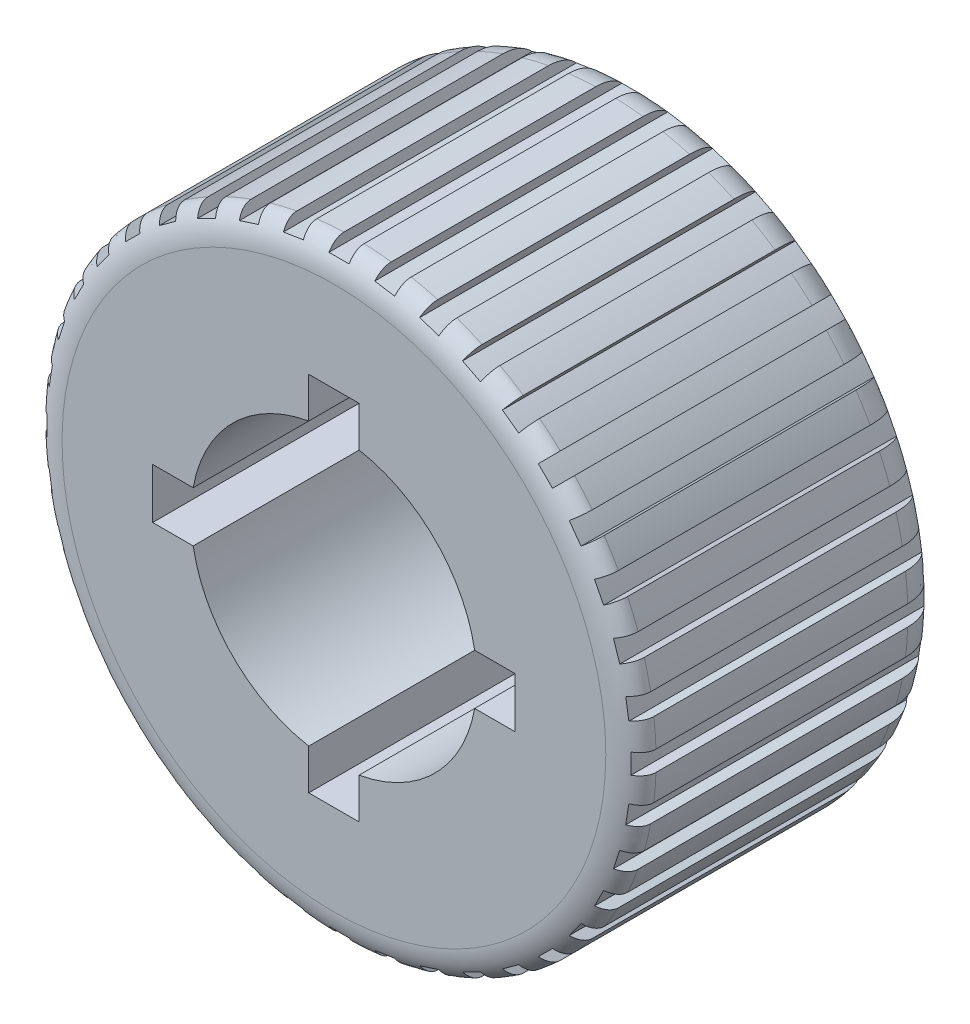
SolidWorks part; units mm, degrees
ref_plane "Plano frontal" through (0, 0, 0) normal (0, 0, 1) x (1, 0, 0)
ref_plane "Plano superior" through (0, 0, 0) normal (0, 1, 0) x (1, 0, 0)
ref_plane "Plano direito" through (0, 0, 0) normal (1, 0, 0) x (0, 0, -1)
sketch "Esboço1" plane through (0, 0, 0) normal (0, 0, 1) x (1, 0, 0)
  circle A0 centre (0, 0) radius 30
  circle A1 centre (0, 0) radius 10.7
  circle A2 centre (0, 0) radius 6.1
  circle A3 centre (0, 0) radius 8.9
  circle A4 centre (0, 0) radius 4.3
  dimension "D1" = 60
extrude "Ressalto-extrusão1" add sketch "Esboço1" along normal blind 30 contours A0 A1 region at (-29.1515, 0, 0)
sketch "Esboço2" plane through (0, 0, 0) normal (0, 0, -1) x (-1, 0, 0)
  circle A1 centre (0, 0) radius 10.7 construction
  circle A3 centre (0, 0) radius 10.7
  circle A4 centre (0, 0) radius 14.2
  dimension "D1" = 28.4
extrude "Corte-extrusão1" cut sketch "Esboço2" against normal through all
sketch "Esboço4" plane through (0, 0, 0) normal (0, 1, 0) x (1, 0, 0)
  line L0 (-29, -8.5) -> (-29, -9.5)
  line L2 (-30, -2) -> (-30, -3)
  line L4 (0, 0) -> (0, 11.1523) construction
  line L6 (-29, -29) -> (-30, -29)
  line L7 (-30, -8.5) -> (-30, -9.5)
  line L8 (-29, -35.5) -> (-30, -35.5)
  line L9 (-30, -35.5) -> (-30, -34.5)
  line L10 (-30, -34.5) -> (-29, -34.5)
  line L11 (-30, -29) -> (-30, -28)
  line L12 (-30, -28) -> (-29, -28)
  line L14 (-29, -22.5) -> (-30, -22.5)
  line L15 (-30, -22.5) -> (-30, -21.5)
  line L16 (-30, -21.5) -> (-29, -21.5)
  line L17 (-29, -28) -> (-29, -29)
  line L18 (-29, -16) -> (-30, -16)
  line L19 (-30, -16) -> (-30, -15)
  line L20 (-30, -15) -> (-29, -15)
  line L21 (-29, -21.5) -> (-29, -22.5)
  line L22 (-29, -9.5) -> (-30, -9.5)
  line L23 (-30, -9.5) -> (-30, -8.5)
  line L24 (-30, -8.5) -> (-29, -8.5)
  line L25 (-29, -15) -> (-29, -16)
  line L26 (-29, -3) -> (-30, -3)
  line L27 (-30, -3) -> (-30, -2)
  line L28 (-30, -2) -> (-29, -2)
  line L30 (-29, -2) -> (-29, -3)
  line L31 (-30, -15) -> (-30, -16)
  line L32 (-29, -34.5) -> (-29, -35.5)
  line L33 (-30, 4.5) -> (-29, 4.5)
  line L34 (-30, 3.5) -> (-30, 4.5)
  line L35 (-29, 3.5) -> (-30, 3.5)
  line L37 (-30, -21.5) -> (-30, -22.5)
  line L38 (-30, -28) -> (-30, -29)
  line L39 (-30, -34.5) -> (-30, -35.5)
  point P0 (0, 0)
  dimension "D1" = 7
  dimension "D2" = 29
  dimension "D3" = 30
  dimension "D4" = 2
  dimension "D5" = 3
  dimension "D6" = 8.5
sketch "Esboço5" plane through (0, 0, 30) normal (0, 0, 1) x (1, 0, 0)
  line L0 (0, 0) -> (-39.2966, 0) construction
  line L5 (-1, 29.9833) -> (-1, 28.9828)
  line L6 (1, 29.9833) -> (1, 28.9828)
  arc A3 (1, 29.9833) -> (-1, 29.9833) centre (0, 0) ccw
  arc A4 (1, 28.9828) -> (-1, 28.9828) centre (0, 0) ccw
fillet "Filete2" radius 2 2 edges at (30, 0, 0) (30, 0, 30) second distance 3 first distance on face at (-14.2, 0, 0) first distance on face at (30, 0, 30)
sketch "Esboço6" plane through (0, 0, 30) normal (0, 0, 1) x (1, 0, 0)
  line L0 (5.5216, 28.4695) -> (5.6781, 29.4577)
  line L1 (3.7027, 29.7706) -> (3.5462, 28.7824)
  line L2 (-1, 29.9833) -> (-1, 28.9828)
  line L3 (1, 28.9828) -> (1, 29.9833)
  line L4 (-1, 29.9833) -> (-1, 28.9828)
  line L5 (1, 28.9828) -> (1, 29.9833)
  line L6 (9.9072, 27.2552) -> (10.2164, 28.2068)
  line L7 (8.3143, 28.8249) -> (8.0051, 27.8733)
  line L8 (14.0489, 25.3698) -> (14.5032, 26.2614)
  line L9 (12.7211, 27.1693) -> (12.2669, 26.2778)
  line L10 (17.8447, 22.8598) -> (18.4328, 23.6692)
  line L11 (16.8147, 24.8448) -> (16.2266, 24.0353)
  line L12 (21.201, 19.7868) -> (21.9085, 20.4943)
  line L13 (20.4943, 21.9085) -> (19.7868, 21.201)
  line L14 (24.0353, 16.2266) -> (24.8448, 16.8147)
  line L15 (23.6692, 18.4328) -> (22.8598, 17.8447)
  line L16 (26.2778, 12.2669) -> (27.1693, 12.7211)
  line L17 (26.2614, 14.5032) -> (25.3698, 14.0489)
  line L18 (27.8733, 8.0051) -> (28.8249, 8.3143)
  line L19 (28.2068, 10.2164) -> (27.2552, 9.9072)
  line L20 (28.7824, 3.5462) -> (29.7706, 3.7027)
  line L21 (29.4577, 5.6781) -> (28.4695, 5.5216)
  line L22 (28.9828, -1) -> (29.9833, -1)
  line L23 (29.9833, 1) -> (28.9828, 1)
  line L24 (28.4695, -5.5216) -> (29.4577, -5.6781)
  line L25 (29.7706, -3.7027) -> (28.7824, -3.5462)
  line L26 (27.2552, -9.9072) -> (28.2068, -10.2164)
  line L27 (28.8249, -8.3143) -> (27.8733, -8.0051)
  line L28 (25.3698, -14.0489) -> (26.2614, -14.5032)
  line L29 (27.1693, -12.7211) -> (26.2778, -12.2669)
  line L30 (22.8598, -17.8447) -> (23.6692, -18.4328)
  line L31 (24.8448, -16.8147) -> (24.0353, -16.2266)
  line L32 (19.7868, -21.201) -> (20.4943, -21.9085)
  line L33 (21.9085, -20.4943) -> (21.201, -19.7868)
  line L34 (16.2266, -24.0353) -> (16.8147, -24.8448)
  line L35 (18.4328, -23.6692) -> (17.8447, -22.8598)
  line L36 (12.2669, -26.2778) -> (12.7211, -27.1693)
  line L37 (14.5032, -26.2614) -> (14.0489, -25.3698)
  line L38 (8.0051, -27.8733) -> (8.3143, -28.8249)
  line L39 (10.2164, -28.2068) -> (9.9072, -27.2552)
  line L40 (3.5462, -28.7824) -> (3.7027, -29.7706)
  line L41 (5.6781, -29.4577) -> (5.5216, -28.4695)
  line L42 (-1, -28.9828) -> (-1, -29.9833)
  line L43 (1, -29.9833) -> (1, -28.9828)
  line L44 (-5.5216, -28.4695) -> (-5.6781, -29.4577)
  line L45 (-3.7027, -29.7706) -> (-3.5462, -28.7824)
  line L46 (-9.9072, -27.2552) -> (-10.2164, -28.2068)
  line L47 (-8.3143, -28.8249) -> (-8.0051, -27.8733)
  line L48 (-14.0489, -25.3698) -> (-14.5032, -26.2614)
  line L49 (-12.7211, -27.1693) -> (-12.2669, -26.2778)
  line L50 (-17.8447, -22.8598) -> (-18.4328, -23.6692)
  line L51 (-16.8147, -24.8448) -> (-16.2266, -24.0353)
  line L52 (-21.201, -19.7868) -> (-21.9085, -20.4943)
  line L53 (-20.4943, -21.9085) -> (-19.7868, -21.201)
  line L54 (-24.0353, -16.2266) -> (-24.8448, -16.8147)
  line L55 (-23.6692, -18.4328) -> (-22.8598, -17.8447)
  line L56 (-26.2778, -12.2669) -> (-27.1693, -12.7211)
  line L57 (-26.2614, -14.5032) -> (-25.3698, -14.0489)
  line L58 (-27.8733, -8.0051) -> (-28.8249, -8.3143)
  line L59 (-28.2068, -10.2164) -> (-27.2552, -9.9072)
  line L60 (-28.7824, -3.5462) -> (-29.7706, -3.7027)
  line L61 (-29.4577, -5.6781) -> (-28.4695, -5.5216)
  line L62 (-28.9828, 1) -> (-29.9833, 1)
  line L63 (-29.9833, -1) -> (-28.9828, -1)
  line L64 (-28.4695, 5.5216) -> (-29.4577, 5.6781)
  line L65 (-29.7706, 3.7027) -> (-28.7824, 3.5462)
  line L66 (-27.2552, 9.9072) -> (-28.2068, 10.2164)
  line L67 (-28.8249, 8.3143) -> (-27.8733, 8.0051)
  line L68 (-25.3698, 14.0489) -> (-26.2614, 14.5032)
  line L69 (-27.1693, 12.7211) -> (-26.2778, 12.2669)
  line L70 (-22.8598, 17.8447) -> (-23.6692, 18.4328)
  line L71 (-24.8448, 16.8147) -> (-24.0353, 16.2266)
  line L72 (-19.7868, 21.201) -> (-20.4943, 21.9085)
  line L73 (-21.9085, 20.4943) -> (-21.201, 19.7868)
  line L74 (-16.2266, 24.0353) -> (-16.8147, 24.8448)
  line L75 (-18.4328, 23.6692) -> (-17.8447, 22.8598)
  line L76 (-12.2669, 26.2778) -> (-12.7211, 27.1693)
  line L77 (-14.5032, 26.2614) -> (-14.0489, 25.3698)
  line L78 (-8.0051, 27.8733) -> (-8.3143, 28.8249)
  line L79 (-10.2164, 28.2068) -> (-9.9072, 27.2552)
  line L80 (-3.5462, 28.7824) -> (-3.7027, 29.7706)
  line L81 (-5.6781, 29.4577) -> (-5.5216, 28.4695)
  arc A0 (5.5216, 28.4695) -> (3.5462, 28.7824) centre (0, 0) ccw
  arc A1 (5.6781, 29.4577) -> (3.7027, 29.7706) centre (0, 0) ccw
  arc A2 (1, 28.9828) -> (-1, 28.9828) centre (0, 0) ccw
  arc A3 (1, 29.9833) -> (-1, 29.9833) centre (0, 0) ccw
  arc A4 (1, 28.9828) -> (-1, 28.9828) centre (0, 0) ccw
  arc A5 (1, 29.9833) -> (-1, 29.9833) centre (0, 0) ccw
  arc A6 (9.9072, 27.2552) -> (8.0051, 27.8733) centre (0, 0) ccw
  arc A7 (10.2164, 28.2068) -> (8.3143, 28.8249) centre (0, 0) ccw
  arc A8 (14.0489, 25.3698) -> (12.2669, 26.2778) centre (0, 0) ccw
  arc A9 (14.5032, 26.2614) -> (12.7211, 27.1693) centre (0, 0) ccw
  arc A10 (17.8447, 22.8598) -> (16.2266, 24.0353) centre (0, 0) ccw
  arc A11 (18.4328, 23.6692) -> (16.8147, 24.8448) centre (0, 0) ccw
  arc A12 (21.201, 19.7868) -> (19.7868, 21.201) centre (0, 0) ccw
  arc A13 (21.9085, 20.4943) -> (20.4943, 21.9085) centre (0, 0) ccw
  arc A14 (24.0353, 16.2266) -> (22.8598, 17.8447) centre (0, 0) ccw
  arc A15 (24.8448, 16.8147) -> (23.6692, 18.4328) centre (0, 0) ccw
  arc A16 (26.2778, 12.2669) -> (25.3698, 14.0489) centre (0, 0) ccw
  arc A17 (27.1693, 12.7211) -> (26.2614, 14.5032) centre (0, 0) ccw
  arc A18 (27.8733, 8.0051) -> (27.2552, 9.9072) centre (0, 0) ccw
  arc A19 (28.8249, 8.3143) -> (28.2068, 10.2164) centre (0, 0) ccw
  arc A20 (28.7824, 3.5462) -> (28.4695, 5.5216) centre (0, 0) ccw
  arc A21 (29.7706, 3.7027) -> (29.4577, 5.6781) centre (0, 0) ccw
  arc A22 (28.9828, -1) -> (28.9828, 1) centre (0, 0) ccw
  arc A23 (29.9833, -1) -> (29.9833, 1) centre (0, 0) ccw
  arc A24 (28.4695, -5.5216) -> (28.7824, -3.5462) centre (0, 0) ccw
  arc A25 (29.4577, -5.6781) -> (29.7706, -3.7027) centre (0, 0) ccw
  arc A26 (27.2552, -9.9072) -> (27.8733, -8.0051) centre (0, 0) ccw
  arc A27 (28.2068, -10.2164) -> (28.8249, -8.3143) centre (0, 0) ccw
  arc A28 (25.3698, -14.0489) -> (26.2778, -12.2669) centre (0, 0) ccw
  arc A29 (26.2614, -14.5032) -> (27.1693, -12.7211) centre (0, 0) ccw
  arc A30 (22.8598, -17.8447) -> (24.0353, -16.2266) centre (0, 0) ccw
  arc A31 (23.6692, -18.4328) -> (24.8448, -16.8147) centre (0, 0) ccw
  arc A32 (19.7868, -21.201) -> (21.201, -19.7868) centre (0, 0) ccw
  arc A33 (20.4943, -21.9085) -> (21.9085, -20.4943) centre (0, 0) ccw
  arc A34 (16.2266, -24.0353) -> (17.8447, -22.8598) centre (0, 0) ccw
  arc A35 (16.8147, -24.8448) -> (18.4328, -23.6692) centre (0, 0) ccw
  arc A36 (12.2669, -26.2778) -> (14.0489, -25.3698) centre (0, 0) ccw
  arc A37 (12.7211, -27.1693) -> (14.5032, -26.2614) centre (0, 0) ccw
  arc A38 (8.0051, -27.8733) -> (9.9072, -27.2552) centre (0, 0) ccw
  arc A39 (8.3143, -28.8249) -> (10.2164, -28.2068) centre (0, 0) ccw
  arc A40 (3.5462, -28.7824) -> (5.5216, -28.4695) centre (0, 0) ccw
  arc A41 (3.7027, -29.7706) -> (5.6781, -29.4577) centre (0, 0) ccw
  arc A42 (-1, -28.9828) -> (1, -28.9828) centre (0, 0) ccw
  arc A43 (-1, -29.9833) -> (1, -29.9833) centre (0, 0) ccw
  arc A44 (-5.5216, -28.4695) -> (-3.5462, -28.7824) centre (0, 0) ccw
  arc A45 (-5.6781, -29.4577) -> (-3.7027, -29.7706) centre (0, 0) ccw
  arc A46 (-9.9072, -27.2552) -> (-8.0051, -27.8733) centre (0, 0) ccw
  arc A47 (-10.2164, -28.2068) -> (-8.3143, -28.8249) centre (0, 0) ccw
  arc A48 (-14.0489, -25.3698) -> (-12.2669, -26.2778) centre (0, 0) ccw
  arc A49 (-14.5032, -26.2614) -> (-12.7211, -27.1693) centre (0, 0) ccw
  arc A50 (-17.8447, -22.8598) -> (-16.2266, -24.0353) centre (0, 0) ccw
  arc A51 (-18.4328, -23.6692) -> (-16.8147, -24.8448) centre (0, 0) ccw
  arc A52 (-21.201, -19.7868) -> (-19.7868, -21.201) centre (0, 0) ccw
  arc A53 (-21.9085, -20.4943) -> (-20.4943, -21.9085) centre (0, 0) ccw
  arc A54 (-24.0353, -16.2266) -> (-22.8598, -17.8447) centre (0, 0) ccw
  arc A55 (-24.8448, -16.8147) -> (-23.6692, -18.4328) centre (0, 0) ccw
  arc A56 (-26.2778, -12.2669) -> (-25.3698, -14.0489) centre (0, 0) ccw
  arc A57 (-27.1693, -12.7211) -> (-26.2614, -14.5032) centre (0, 0) ccw
  arc A58 (-27.8733, -8.0051) -> (-27.2552, -9.9072) centre (0, 0) ccw
  arc A59 (-28.8249, -8.3143) -> (-28.2068, -10.2164) centre (0, 0) ccw
  arc A60 (-28.7824, -3.5462) -> (-28.4695, -5.5216) centre (0, 0) ccw
  arc A61 (-29.7706, -3.7027) -> (-29.4577, -5.6781) centre (0, 0) ccw
  arc A62 (-28.9828, 1) -> (-28.9828, -1) centre (0, 0) ccw
  arc A63 (-29.9833, 1) -> (-29.9833, -1) centre (0, 0) ccw
  arc A64 (-28.4695, 5.5216) -> (-28.7824, 3.5462) centre (0, 0) ccw
  arc A65 (-29.4577, 5.6781) -> (-29.7706, 3.7027) centre (0, 0) ccw
  arc A66 (-27.2552, 9.9072) -> (-27.8733, 8.0051) centre (0, 0) ccw
  arc A67 (-28.2068, 10.2164) -> (-28.8249, 8.3143) centre (0, 0) ccw
  arc A68 (-25.3698, 14.0489) -> (-26.2778, 12.2669) centre (0, 0) ccw
  arc A69 (-26.2614, 14.5032) -> (-27.1693, 12.7211) centre (0, 0) ccw
  arc A70 (-22.8598, 17.8447) -> (-24.0353, 16.2266) centre (0, 0) ccw
  arc A71 (-23.6692, 18.4328) -> (-24.8448, 16.8147) centre (0, 0) ccw
  arc A72 (-19.7868, 21.201) -> (-21.201, 19.7868) centre (0, 0) ccw
  arc A73 (-20.4943, 21.9085) -> (-21.9085, 20.4943) centre (0, 0) ccw
  arc A74 (-16.2266, 24.0353) -> (-17.8447, 22.8598) centre (0, 0) ccw
  arc A75 (-16.8147, 24.8448) -> (-18.4328, 23.6692) centre (0, 0) ccw
  arc A76 (-12.2669, 26.2778) -> (-14.0489, 25.3698) centre (0, 0) ccw
  arc A77 (-12.7211, 27.1693) -> (-14.5032, 26.2614) centre (0, 0) ccw
  arc A78 (-8.0051, 27.8733) -> (-9.9072, 27.2552) centre (0, 0) ccw
  arc A79 (-8.3143, 28.8249) -> (-10.2164, 28.2068) centre (0, 0) ccw
  arc A80 (-3.5462, 28.7824) -> (-5.5216, 28.4695) centre (0, 0) ccw
  arc A81 (-3.7027, 29.7706) -> (-5.6781, 29.4577) centre (0, 0) ccw
  point P165 (0, 0)
  dimension "D1" = 0
  dimension "D2" = 40
extrude "Corte-extrusão2" cut sketch "Esboço6" against normal through all
sketch "Esboço7" plane through (0, 0, 0) normal (0, 0, -1) x (-1, 0, 0)
  line L0 (18, 0) -> (18, 2.5)
  line L1 (-200000, 0) -> (200039.2966, 0) construction
  line L2 (0, 18) -> (-2.5, 18)
  line L3 (0, 18) -> (2.5, 18)
  line L4 (-2.5, 18) -> (-2.5, 13.9782)
  line L5 (2.5, 18) -> (2.5, 13.9782)
  line L6 (-200000, 0) -> (200039.2966, 0)
  line L7 (0, 0) -> (-42.3655, 0) construction
  line L8 (2.5, -18) -> (2.5, -13.9782)
  line L9 (-2.5, -18) -> (-2.5, -13.9782)
  line L10 (0, -18) -> (2.5, -18)
  line L11 (0, -18) -> (-2.5, -18)
  line L12 (18, 0) -> (18, -2.5)
  line L13 (18, 2.5) -> (13.9782, 2.5)
  line L14 (18, -2.5) -> (13.9782, -2.5)
  line L15 (-18, -2.5) -> (-13.9782, -2.5)
  line L16 (-18, 2.5) -> (-13.9782, 2.5)
  line L17 (-18, 0) -> (-18, -2.5)
  line L18 (-18, 0) -> (-18, 2.5)
  line L19 (0, -18) -> (2.5, -18)
  line L20 (0, -18) -> (-2.5, -18)
  line L21 (2.5, -18) -> (2.5, -13.9782)
  line L22 (-2.5, -18) -> (-2.5, -13.9782)
  line L23 (-2.5, 18) -> (-2.5, 13.9782)
  line L24 (2.5, 18) -> (2.5, 13.9782)
  line L25 (0, 18) -> (-2.5, 18)
  line L26 (0, 18) -> (2.5, 18)
  line L27 (-18, 0) -> (-18, -2.5)
  line L28 (-18, 0) -> (-18, 2.5)
  line L29 (-18, -2.5) -> (-13.9782, -2.5)
  line L30 (-18, 2.5) -> (-13.9782, 2.5)
  line L31 (18, 2.5) -> (13.9782, 2.5)
  line L32 (18, -2.5) -> (13.9782, -2.5)
  line L33 (18, 0) -> (18, 2.5)
  line L34 (18, 0) -> (18, -2.5)
  circle A0 centre (0, 0) radius 14.2 construction
  arc A1 (-2.5, -13.9782) -> (2.5, -13.9782) centre (0, 0) ccw
  arc A2 (2.5, 13.9782) -> (-2.5, 13.9782) centre (0, 0) ccw
  arc A3 (-13.9782, 2.5) -> (-13.9782, -2.5) centre (0, 0) ccw
  arc A4 (13.9782, -2.5) -> (13.9782, 2.5) centre (0, 0) ccw
  arc A5 (2.5, 13.9782) -> (-2.5, 13.9782) centre (0, 0) ccw
  arc A6 (-2.5, -13.9782) -> (2.5, -13.9782) centre (0, 0) ccw
  arc A7 (13.9782, -2.5) -> (13.9782, 2.5) centre (0, 0) ccw
  arc A8 (-13.9782, 2.5) -> (-13.9782, -2.5) centre (0, 0) ccw
  point P49 (0, 0)
  dimension "D1" = 2.5
  dimension "D2" = 2.5
  dimension "D3" = 18
  dimension "D4" = 4
extrude "Corte-extrusão3" cut sketch "Esboço7" against normal through all contours A3 L15 L17 L18 L16 | A1 L8 L10 L11 L9 | L13 A4 L14 L12 L0 | L5 A2 L4 L2 L3
